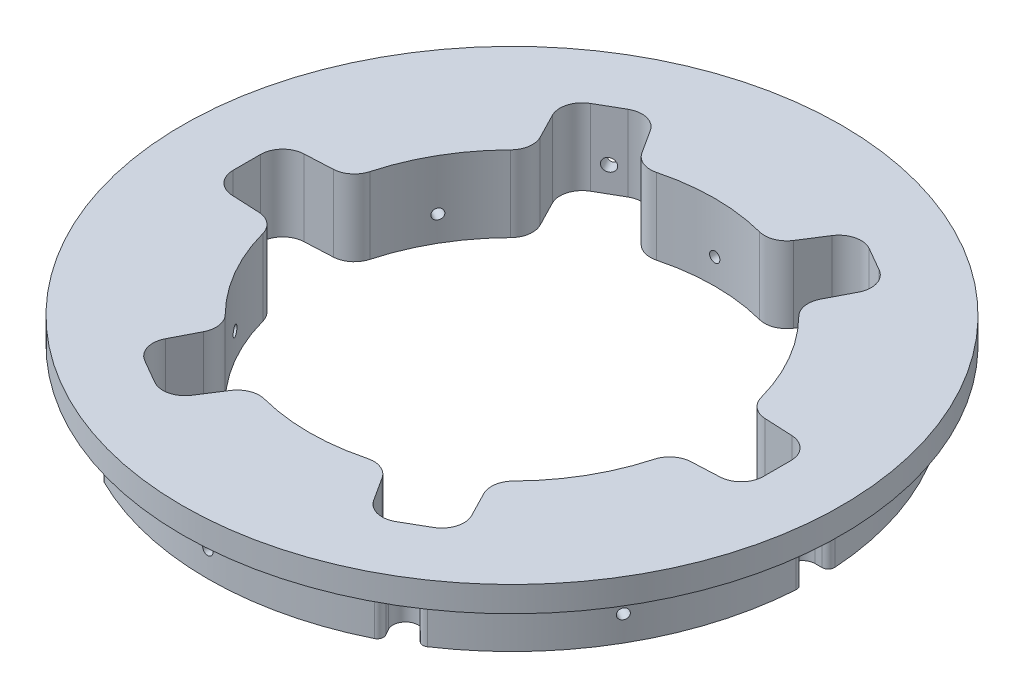
SolidWorks part; units mm, degrees
material "6061-T6 (SS)"
ref_plane "Front Plane" through (0, 0, 0) normal (0, 0, 1) x (1, 0, 0)
ref_plane "Top Plane" through (0, 0, 0) normal (0, 1, 0) x (1, 0, 0)
ref_plane "Right Plane" through (0, 0, 0) normal (1, 0, 0) x (0, 0, -1)
sketch "Sketch1" plane through (0, 0, 0) normal (0, 1, 0) x (1, 0, 0)
  circle A0 centre (0, 0) radius 76.2
  circle A1 centre (0, 0) radius 50.8
  dimension "D1" = 152.4
  dimension "D2" = 101.6
extrude "Boss-Extrude1" add sketch "Sketch1" against normal blind 19.05
sketch "Sketch3" plane through (0, -19.05, 0) normal (0, -1, 0) x (-1, 0, 0)
  line L0 (-76.1338, 3.175) -> (-72.771, 3.175)
  line L1 (-76.1338, -3.175) -> (-72.771, -3.175)
  circle A0 centre (0, 0) radius 76.2 construction
  arc A1 (-72.771, 3.175) -> (-72.771, -3.175) centre (-72.771, 0) cw
  arc A2 (-76.1338, -3.175) -> (-76.1338, 3.175) centre (0, 0) cw
  point P9 (-69.596, 0)
  point P13 (-76.2, 0)
  dimension "D1" = 6.35
  dimension "D2" = 6.604
extrude "Cut-Extrude1" cut sketch "Sketch3" against normal blind 12.7
sketch "Sketch4" plane through (0, -19.05, 0) normal (0, -1, 0) x (-1, 0, 0)
  line L0 (-66.421, 8.7312) -> (-66.421, -8.7312)
  line L1 (-66.421, -8.7312) -> (-49.899, -9.525)
  line L2 (-49.899, -9.525) -> (-49.899, 9.525)
  line L3 (-49.899, 9.525) -> (-66.421, 8.7312)
  line L4 (-66.421, 0) -> (0, 0) construction
  circle A0 centre (0, 0) radius 50.8 construction
  dimension "D1" = 3.175
  dimension "D2" = 19.05
  dimension "D3" = 17.4625
extrude "Cut-Extrude2" cut sketch "Sketch4" against normal through all
hole_wizard "1/8 (0.125) Diameter Hole2" positions "Sketch5" profile "Sketch6" hole size "1/8" standard "ANSI Inch" end condition through all
sketch "Sketch5" plane through (66.421, 0, 0) normal (-1, 0, 0) x (0, 0, 1)
  line L0 (-8.7312, -19.05) -> (8.7312, -19.05) construction
  point P0 (0, -12.7)
  dimension "D1" = 6.35
sketch "Sketch6" plane through (66.421, -12.7, 0) normal (0, 1, 0) x (0, 0, 1)
  line L0 (0, 0) -> (0, 9.779)
  line L1 (0, 9.779) -> (1.5875, 9.779)
  line L2 (1.5875, 9.779) -> (1.5875, 0)
  line L5 (1.5875, 0) -> (0, 0)
  line L11 (0, -6.35) -> (0, 107.95) construction
  dimension "Thru Hole Dia." = 3.175
  dimension "Thru Hole Depth" = 9.779
fillet "Fillet1" radius 1.5875 2 edges at (76.1338, -12.7, 3.175) (76.1338, -12.7, -3.175)
fillet "Fillet2" radius 5.5562 4 edges at (66.421, -9.525, 8.7312) (66.421, -9.525, -8.7312) (49.899, -9.525, 9.525) (49.899, -9.525, -9.525)
sketch "Sketch11" plane through (0, 0, 0) normal (0, 0, 1) x (1, 0, 0)
  line L0 (-76.2, -19.05) -> (76.0446, -19.05) construction
  circle A0 centre (0, -12.7) radius 1.2891
  point P2 (0, 0)
  dimension "D1" = 2.5781
  dimension "D2" = 6.35
extrude "Cut-Extrude4" cut sketch "Sketch11" against normal through all
pattern_circular "CirPattern1" count 6 over 360 about axis through (0, -19.05, 0) along (0, 1, 0) of "Cut-Extrude1", "Cut-Extrude2", "Fillet2", "Fillet1", "1/8 (0.125) Diameter Hole2", "Cut-Extrude4"
sketch "Sketch8" plane through (0, 0, 0) normal (0, 1, 0) x (1, 0, 0)
  circle A0 centre (0, 0) radius 82.55
  circle A1 centre (0, 0) radius 76.2
  circle A2 centre (0, 0) radius 76.2 construction
  dimension "D1" = 6.35
extrude "Boss-Extrude3" add sketch "Sketch8" against normal up to surface (6.35 mm away) up to face at (-74.0439, -6.35, 0)
